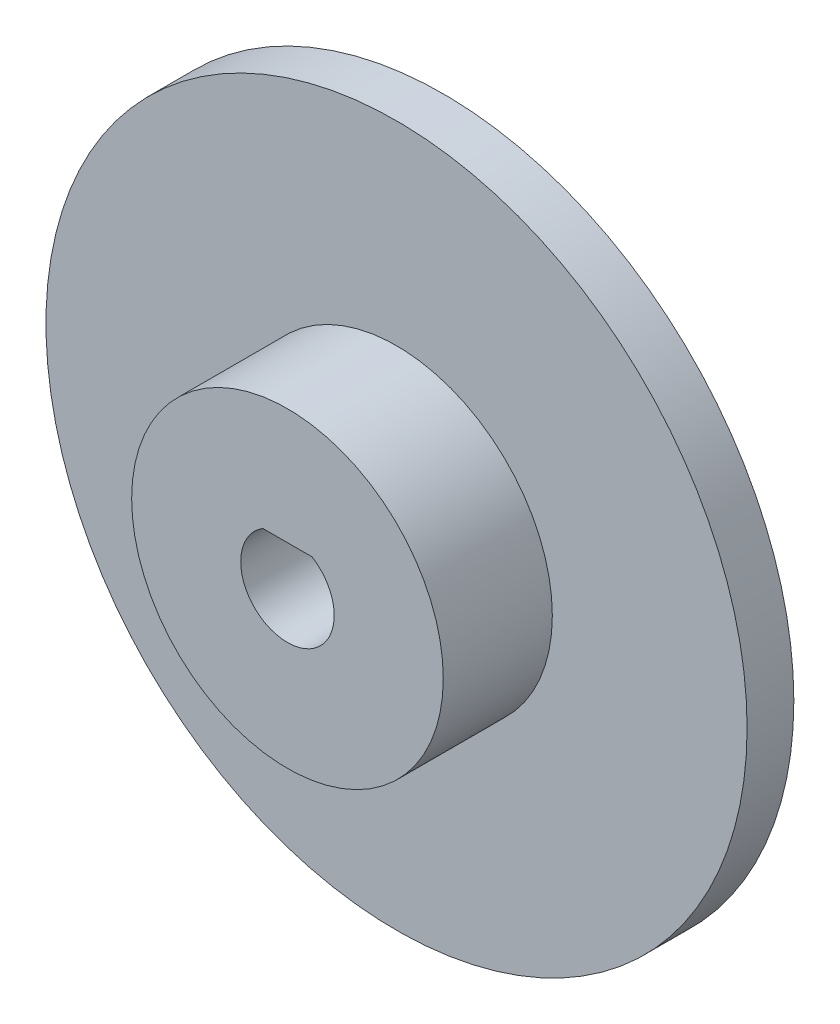
SolidWorks part; units mm, degrees
material "ABS"
ref_plane "Front Plane" through (0, 0, 0) normal (0, 0, 1) x (1, 0, 0)
ref_plane "Top Plane" through (0, 0, 0) normal (0, 1, 0) x (1, 0, 0)
ref_plane "Right Plane" through (0, 0, 0) normal (1, 0, 0) x (0, 0, -1)
sketch "Sketch1" plane through (0, 0, 0) normal (0, 0, 1) x (1, 0, 0)
  line L0 (-1.5803, 2.55) -> (1.5803, 2.55)
  circle A0 centre (0, 0) radius 22.5
  circle A1 centre (0, 0) radius 3
  circle A2 centre (0, 0) radius 10
  dimension "D1" = 45
  dimension "D2" = 6
  dimension "D4" = 20
  dimension "D3" = 2.55
extrude "Boss-Extrude1" add sketch "Sketch1" along normal blind 3 contours A0 A1 | L0 A1 | A0 A2 region at (0, 2.7312, 0) region at (-21.8636, 0, 0) region at (-9.7172, 0, 0)
sketch "Sketch2" plane through (0, 0, 3) normal (0, 0, 1) x (1, 0, 0)
  circle A0 centre (0, 0) radius 22.5
extrude "Boss-Extrude2" add sketch "Sketch1<3>" along normal blind 10 contours A2 A1 | L0 A1 region at (0, 2.7312, 0) region at (-9.7172, 0, 0)
sketch "Sketch1<3>" plane through (0, 0, 0) normal (0, 0, 1) x (1, 0, 0) same geometry as "Sketch1"
